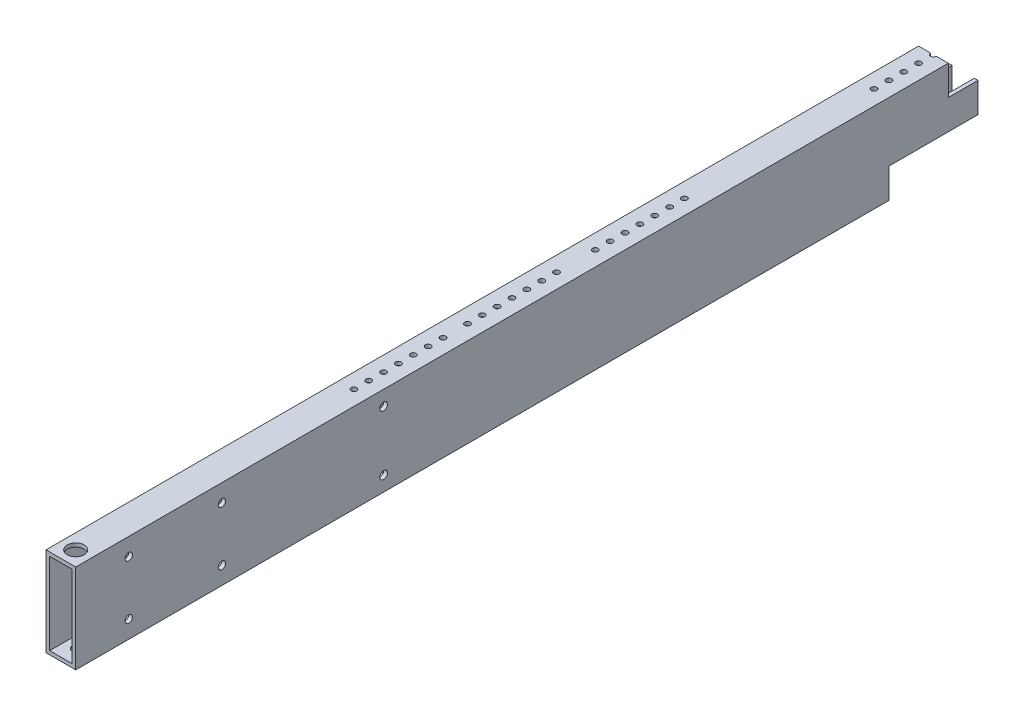
SolidWorks part; units mm, degrees
ref_plane "Front Plane" through (0, 0, 0) normal (0, 0, 1) x (1, 0, 0)
ref_plane "Top Plane" through (0, 0, 0) normal (0, 1, 0) x (1, 0, 0)
ref_plane "Right Plane" through (0, 0, 0) normal (1, 0, 0) x (0, 0, -1)
sketch "Sketch1" plane through (0, 0, 0) normal (0, 0, 1) x (1, 0, 0)
  line L1 (-12.7, -38.1) -> (12.7, -38.1)
  line L2 (-12.7, -38.1) -> (-12.7, 38.1)
  line L3 (-12.7, 38.1) -> (12.7, 38.1)
  line L4 (12.7, -38.1) -> (12.7, 38.1)
  line L5 (-12.7, -38.1) -> (12.7, 38.1) construction
  line L6 (-12.7, 38.1) -> (12.7, -38.1) construction
  point P0 (0, 0)
  dimension "D1" = 25.4
  dimension "D2" = 76.2
extrude "Boss-Extrude1" add sketch "Sketch1" along normal mid plane 771.398
shell "Shell1" thickness 3.175 removed face at (0, 0, -385.699) removed face at (0, 0, 385.699)
sketch "Sketch2" plane through (12.7, 0, 0) normal (1, 0, 0) x (0, 0, -1)
  line L1 (385.699, -38.1) -> (309.499, -38.1)
  line L2 (385.699, -38.1) -> (385.699, -12.7)
  line L3 (385.699, -12.7) -> (309.499, -12.7)
  line L4 (309.499, -38.1) -> (309.499, -12.7)
  dimension "D1" = 25.4
  dimension "D2" = 76.2
extrude "Cut-Extrude1" cut sketch "Sketch2" against normal through all
sketch "Sketch3" plane through (12.7, 0, 0) normal (1, 0, 0) x (0, 0, -1)
  line L1 (385.699, 38.1) -> (360.299, 38.1)
  line L2 (385.699, 38.1) -> (385.699, 12.7)
  line L3 (385.699, 12.7) -> (360.299, 12.7)
  line L4 (360.299, 38.1) -> (360.299, 12.7)
  dimension "D1" = 25.4
extrude "Cut-Extrude2" cut sketch "Sketch3" against normal through all
sketch "Sketch4" plane through (0, 38.1, 0) normal (0, 1, 0) x (1, 0, 0)
  line L0 (-12.7, 360.299) -> (12.7, 360.299) construction
  circle A0 centre (0, 147.3945) radius 2.3812
  circle A1 centre (0, 134.6945) radius 2.3812
  circle A2 centre (0, 121.9945) radius 2.3812
  circle A3 centre (0, 109.2945) radius 2.3812
  circle A4 centre (0, 96.5945) radius 2.3812
  circle A5 centre (0, 83.8945) radius 2.3812
  circle A6 centre (0, 71.1945) radius 2.3812
  circle A7 centre (0, 38.0987) radius 2.3812
  circle A8 centre (0, 25.3987) radius 2.3813
  circle A9 centre (0, 12.6987) radius 2.3813
  circle A10 centre (0, -0.0013) radius 2.3813
  circle A11 centre (0, -12.7013) radius 2.3812
  circle A12 centre (0, -25.4013) radius 2.3812
  circle A13 centre (0, -38.1013) radius 2.3812
  circle A15 centre (0, -58.9932) radius 2.3812
  circle A16 centre (0, -71.6932) radius 2.3812
  circle A17 centre (0, -84.3932) radius 2.3812
  circle A18 centre (0, -97.0932) radius 2.3812
  circle A19 centre (0, -109.7932) radius 2.3812
  circle A20 centre (0, -122.4932) radius 2.3812
  circle A21 centre (0, -135.1932) radius 2.3813
  point P33 (0, 360.299)
  dimension "D1" = 4.7625
  dimension "D3" = 12.7
  dimension "D4" = 12.7
  dimension "D5" = 12.7
  dimension "D6" = 12.7
  dimension "D7" = 12.7
  dimension "D8" = 12.7
  dimension "D9" = 322.2003
  dimension "D10" = 12.7
  dimension "D11" = 12.7
  dimension "D12" = 12.7
  dimension "D13" = 12.7
  dimension "D14" = 12.7
  dimension "D15" = 12.7
  dimension "D16" = 12.7
  dimension "D17" = 419.2922
  dimension "D18" = 12.7
  dimension "D19" = 12.7
  dimension "D20" = 12.7
  dimension "D21" = 12.7
  dimension "D22" = 12.7
  dimension "D2" = 212.9045
extrude "Cut-Extrude3" cut sketch "Sketch4" against normal through all
sketch "Sketch5" plane through (0, 38.1, 0) normal (0, 1, 0) x (1, 0, 0)
  line L0 (-12.7, 360.299) -> (12.7, 360.299) construction
  circle A0 centre (0, 360.299) radius 2.3813
  circle A1 centre (0, 347.599) radius 2.3813
  circle A2 centre (0, 334.899) radius 2.3813
  circle A3 centre (0, 322.199) radius 2.3813
  circle A4 centre (0, 309.499) radius 2.3813
  dimension "D1" = 4.7625
  dimension "D3" = 12.7
  dimension "D4" = 12.7
  dimension "D5" = 12.7
  dimension "D8" = 0
  dimension "D2" = 12.7
extrude "Cut-Extrude4" cut sketch "Sketch5" against normal up to next
sketch "Sketch6" plane through (0, -38.1, 0) normal (0, -1, 0) x (1, 0, 0)
  line L0 (-12.7, -309.499) -> (12.7, -309.499) construction
  circle A0 centre (0, -309.499) radius 2.3813
  circle A1 centre (0, -296.799) radius 2.3813
  circle A2 centre (0, -284.099) radius 2.3813
  circle A3 centre (0, -258.699) radius 2.3813
  circle A6 centre (0, -271.399) radius 2.3813
  dimension "D1" = 4.7625
  dimension "D2" = 12.7
  dimension "D3" = 12.7
  dimension "D4" = 12.7
  dimension "D5" = 12.7
  dimension "D6" = 0
extrude "Cut-Extrude5" cut sketch "Sketch6" against normal up to next
sketch3d "3DSketch1" [suppressed]
  line L0 (0, 34.925, -109.2945) -> (0, 38.1, -109.2945) construction
  line L1 (0, 34.925, 97.0932) -> (0, 38.1, 97.0932) construction
  point P0 (0, 38.1, -109.2945)
  point P1 (0, 0, 0)
  point P4 (0, 38.1, 97.0932)
sketch "Sketch11" plane through (12.7, 0, 0) normal (1, 0, 0) x (0, 0, -1)
  point P0 (-340.3244, 23.1254)
  point P1 (-260.7244, 23.1254)
  point P3 (-260.7244, -23.1)
  point P5 (-340.3244, -23.1)
hole_wizard "CBORE for M6 Hex Head Bolt1" positions "Sketch19" profile "Sketch18" counterbore size "M6" standard "Lanco STD" end condition through all
sketch "Sketch19" plane through (-12.7, 0, 0) normal (-1, 0, 0) x (0, 0, 1)
  point P0 (260.7244, 23.1254)
  point P3 (260.7244, -23.1)
  point P6 (340.3244, 23.1254)
  point P9 (340.3244, -23.1)
sketch "Sketch18" plane through (-12.7, 23.1254, 260.7244) normal (0, 1, 0) x (0, 0, 1)
  line L0 (0, 0) -> (0, 25.4)
  line L1 (0, 25.4) -> (3.15, 25.4)
  line L3 (3.15, 25.4) -> (3.15, 4)
  line L4 (3.15, 4) -> (7.2735, 4)
  line L5 (7.2735, 4) -> (7.2735, 0)
  line L7 (7.2735, 0) -> (0, 0)
  line L11 (0, -6.35) -> (0, 107.95) construction
  dimension "Thru Hole Dia." = 6.3
  dimension "Thru Hole Depth" = 25.4
  dimension "C'Bore Dia." = 14.547
  dimension "C'Bore Depth" = 4
hole_wizard "CBORE for M6 Hex Head Cap Screw1" positions "Sketch21" profile "Sketch20" counterbore size "M6" standard "ANSI Metric" end condition through all
sketch "Sketch21" plane through (-12.7, 0, 0) normal (-1, 0, 0) x (0, 0, 1)
  line L0 (385.699, 38.1) -> (-360.299, 38.1) construction
  line L1 (385.699, 38.1) -> (385.699, -38.1) construction
  point P0 (122.4678, 25.4)
  point P2 (122.4678, -25.4)
  dimension "D1" = 12.7
  dimension "D2" = 63.5
  dimension "D3" = 263.2312
  dimension "D4" = 263.2312
sketch "Sketch20" plane through (-12.7, 25.4, 122.4678) normal (0, 1, 0) x (0, 0, 1)
  line L0 (0, 0) -> (0, 25.4)
  line L1 (0, 25.4) -> (3.3, 25.4)
  line L3 (3.3, 25.4) -> (3.3, 4.15)
  line L4 (3.3, 4.15) -> (7.275, 4.15)
  line L5 (7.275, 4.15) -> (7.275, 0)
  line L7 (7.275, 0) -> (0, 0)
  line L11 (0, -6.35) -> (0, 107.95) construction
  dimension "Thru Hole Dia." = 6.6
  dimension "Thru Hole Depth" = 25.4
  dimension "C'Bore Dia." = 14.55
  dimension "C'Bore Depth" = 4.15
hole_wizard "CBORE for M6 Hex Head Cap Screw2" positions "Sketch26" profile "Sketch25" counterbore size "M6" standard "ANSI Metric" end condition through all
sketch "Sketch26" plane through (0, 38.1, 0) normal (0, 1, 0) x (1, 0, 0)
  line L0 (12.7, -385.699) -> (-12.7, -385.699) construction
  point P0 (0, -372.999)
  dimension "D1" = 12.7
sketch "Sketch25" plane through (0, 38.1, 372.999) normal (1, 0, 0) x (0, 0, 1)
  line L0 (0, 0) -> (0, 76.2)
  line L1 (0, 76.2) -> (3.3, 76.2)
  line L3 (3.3, 76.2) -> (3.3, 4.15)
  line L4 (3.3, 4.15) -> (7.275, 4.15)
  line L5 (7.275, 4.15) -> (7.275, 0)
  line L7 (7.275, 0) -> (0, 0)
  line L11 (0, -6.35) -> (0, 107.95) construction
  dimension "Thru Hole Dia." = 6.6
  dimension "Thru Hole Depth" = 76.2
  dimension "C'Bore Dia." = 14.55
  dimension "C'Bore Depth" = 4.15
